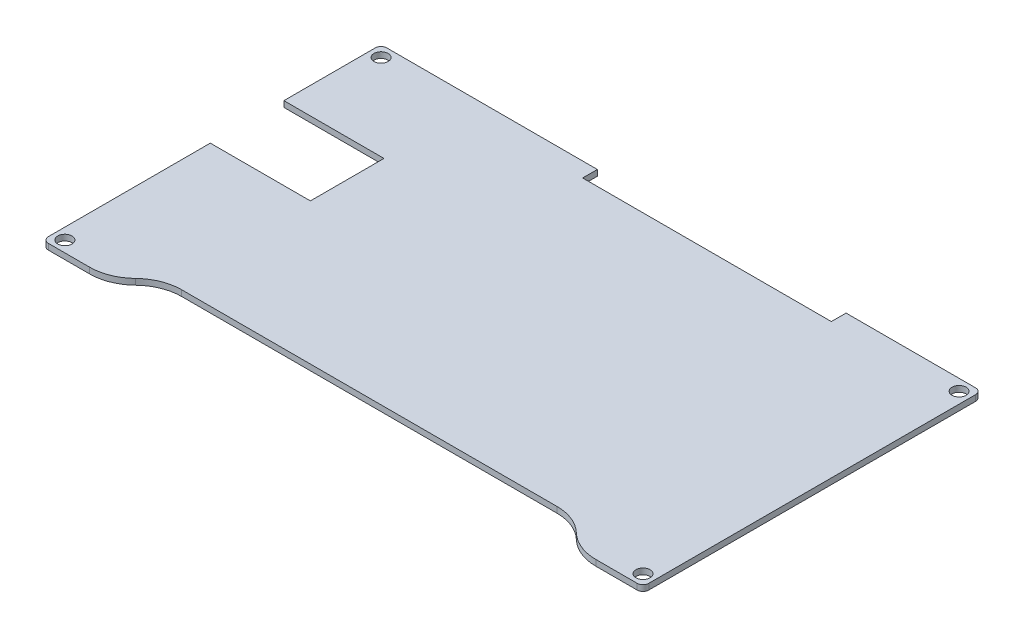
SolidWorks part; units mm, degrees
ref_plane "Ebene vorne" through (0, 0, 0) normal (0, 0, 1) x (1, 0, 0)
ref_plane "Ebene oben" through (0, 0, 0) normal (0, 1, 0) x (1, 0, 0)
ref_plane "Ebene rechts" through (0, 0, 0) normal (1, 0, 0) x (0, 0, -1)
sketch "Skizze1" plane through (0, 0, 0) normal (0, 1, 0) x (1, 0, 0)
  line L1 (-49.1, -26.85) -> (49.1, -26.85) construction
  line L2 (-49.1, -26.85) -> (-49.1, 26.85) construction
  line L3 (-49.1, 26.85) -> (49.1, 26.85) construction
  line L4 (49.1, -26.85) -> (49.1, 26.85) construction
  line L5 (-49.1, -26.85) -> (49.1, 26.85) construction
  line L6 (-49.1, 26.85) -> (49.1, -26.85) construction
  line L7 (-51, -28.75) -> (51, -28.75)
  line L8 (-51, -28.75) -> (-51, 28.75)
  line L9 (-51, 28.75) -> (51, 28.75)
  line L10 (51, -28.75) -> (51, 28.75)
  line L11 (-51, -28.75) -> (51, 28.75) construction
  line L12 (-51, 28.75) -> (51, -28.75) construction
  point P0 (0, 0)
  point P6 (0, 0)
  dimension "D1" = 102
  dimension "D2" = 57.5
  dimension "D3" = 98.2
  dimension "D4" = 53.7
extrude "Aufsatz-Linear austragen1" add sketch "Skizze1" along normal blind 1
hole_wizard "Durchgangsloch für M21" positions "Skizze4" profile "Skizze2" hole size "M2" standard "DIN" end condition up to next
sketch "Skizze4" plane through (0, 0, 0) normal (0, -1, 0) x (-1, 0, 0)
  line L1 (49.1, 26.85) -> (-49.1, 26.85)
  line L2 (49.1, 26.85) -> (49.1, -26.85)
  line L3 (49.1, -26.85) -> (-49.1, -26.85)
  line L4 (-49.1, 26.85) -> (-49.1, -26.85)
  line L5 (49.1, 26.85) -> (-49.1, -26.85) construction
  line L6 (49.1, -26.85) -> (-49.1, 26.85) construction
  point P2 (-49.1, -26.85)
  point P107 (49.1, 26.85)
  point P108 (49.1, -26.85)
  point P109 (-49.1, 26.85)
  dimension "D1" = 98.2
  dimension "D2" = 53.7
sketch "Skizze2" plane through (49.1, 0, 26.85) normal (1, 0, 0) x (0, 0, -1)
  line L0 (0, 0) -> (0, 1)
  line L1 (0, 1) -> (1.2, 1)
  line L2 (1.2, 1) -> (1.2, 0)
  line L5 (1.2, 0) -> (0, 0)
  line L11 (0, -6.35) -> (0, 107.95) construction
  dimension "Bohrerdurchmesser" = 2.4
  dimension "Bohrungstiefe" = 1
fillet "Verrundung1" radius 1 4 edges at (51, 0.5, -28.75) (51, 0.5, 28.75) (-51, 0.5, 28.75) (-51, 0.5, -28.75)
sketch "Skizze5" plane through (0, 1, 0) normal (0, 1, 0) x (1, 0, 0)
  line L0 (-43, -28.75) -> (43, -28.75)
  line L1 (-50, -28.75) -> (50, -28.75) construction
  line L2 (-51, 27.75) -> (-51, -27.75) construction
  line L3 (31.8757, -24.25) -> (-31.8757, -24.25)
  line L4 (51, -27.75) -> (51, 27.75) construction
  arc A0 (-37.4379, -26.5) -> (-43, -28.75) centre (-43, -20.75) cw
  arc A1 (-37.4379, -26.5) -> (-31.8757, -24.25) centre (-31.8757, -32.25) cw
  arc A2 (37.4379, -26.5) -> (31.8757, -24.25) centre (31.8757, -32.25) ccw
  arc A3 (43, -28.75) -> (37.4379, -26.5) centre (43, -20.75) cw
  dimension "D3" = 8
  dimension "D1" = 8
  dimension "D2" = 8
  dimension "D4" = 4.5
extrude "Schnitt-Linear austragen1" cut sketch "Skizze5" against normal up to next
sketch "Skizze6" plane through (0, 1, 0) normal (0, 1, 0) x (1, 0, 0)
  line L0 (28, 28.75) -> (-14.25, 28.75)
  line L1 (50, 28.75) -> (-50, 28.75) construction
  line L2 (-14.25, 28.75) -> (-14.25, 26.25)
  line L3 (-14.25, 26.25) -> (28, 26.25)
  line L4 (28, 26.25) -> (28, 28.75)
  line L5 (51, -27.75) -> (51, 27.75) construction
  line L6 (-51, 27.75) -> (-51, -27.75) construction
  line L7 (-51, 12.25) -> (-34, 12.25)
  line L8 (-34, 12.25) -> (-34, -0.25)
  line L9 (-34, -0.25) -> (-51, -0.25)
  line L10 (-51, -0.25) -> (-51, 12.25)
  dimension "D1" = 42.25
  dimension "D2" = 23
  dimension "D3" = 2.5
  dimension "D4" = 16.5
  dimension "D5" = 12.5
  dimension "D6" = 17
extrude "Schnitt-Linear austragen2" cut sketch "Skizze6" against normal up to next
